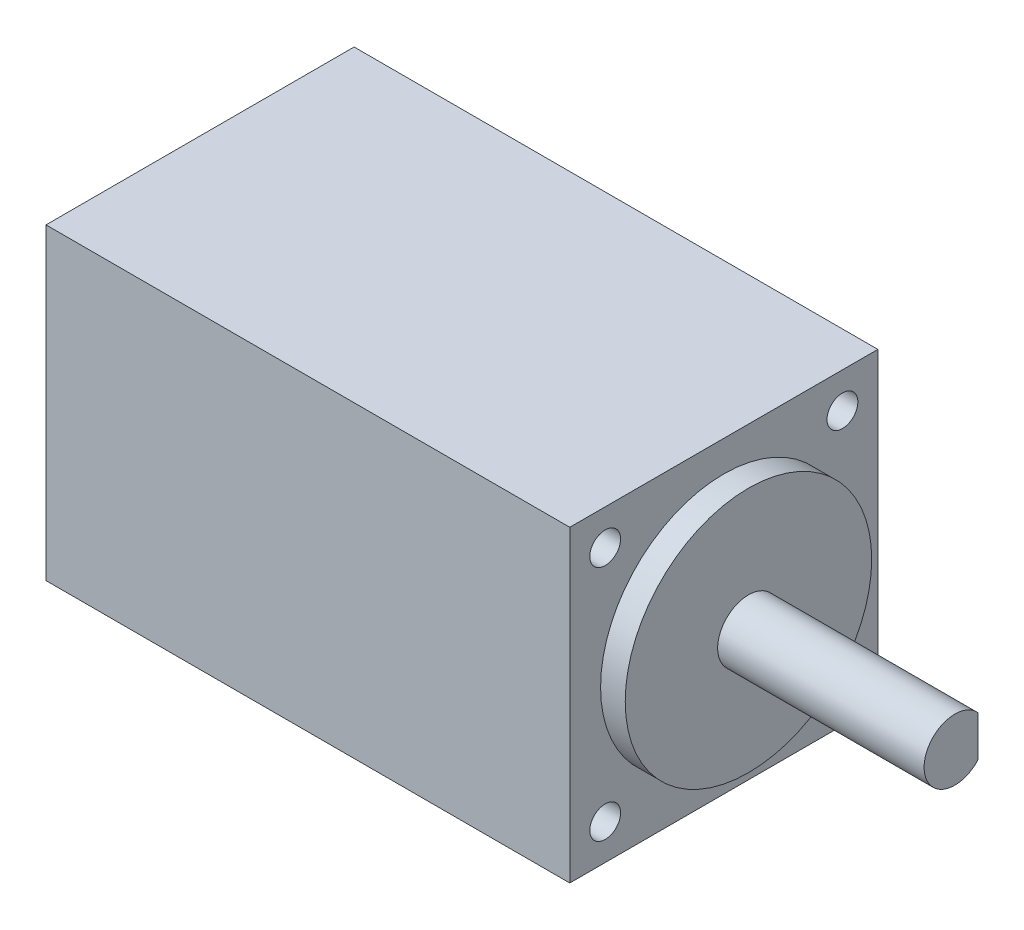
SolidWorks part; units mm, degrees
ref_plane "前视基准面" through (0, 0, 0) normal (0, 0, 1) x (1, 0, 0)
ref_plane "上视基准面" through (0, 0, 0) normal (0, 1, 0) x (1, 0, 0)
ref_plane "右视基准面" through (0, 0, 0) normal (1, 0, 0) x (0, 0, -1)
sketch "草图1" plane through (0, 0, 0) normal (1, 0, 0) x (0, 0, -1)
  line L1 (0, 0) -> (20, 0)
  line L2 (0, 0) -> (0, 20)
  line L3 (0, 20) -> (20, 20)
  line L4 (20, 0) -> (20, 20)
  circle A0 centre (2.3, 2.3) radius 1
  circle A1 centre (2.3, 17.7) radius 1
  circle A2 centre (17.7, 17.7) radius 1
  circle A3 centre (17.7, 2.2986) radius 1
extrude "凸台-拉伸2" add sketch "草图1" along normal blind 34
sketch "草图2" plane through (34, 0, 0) normal (1, 0, 0) x (0, 0, -1)
  circle A0 centre (10, 10) radius 8
extrude "凸台-拉伸3" add sketch "草图2" along normal blind 1.6 contours A0
sketch "草图3" plane through (35.6, 0, 0) normal (1, 0, 0) x (0, 0, -1)
  circle A0 centre (10, 10) radius 2
extrude "凸台-拉伸4" add sketch "草图3" along normal blind 13.4
sketch "草图4" plane through (49, 0, 0) normal (1, 0, 0) x (0, 0, -1)
  line L0 (8, 10) -> (11.5, 10)
  line L1 (11.5, 8.6771) -> (11.5, 11.3229)
  circle A0 centre (10, 10) radius 2 construction
  circle A1 centre (10, 10) radius 2 construction
  circle A2 centre (10, 10) radius 2
  circle M3 centre (10, 10) radius 2
extrude "切除-拉伸1" cut sketch "草图4" against normal blind 9 contours L1 M3 region at (49, 10, -11.7023)
